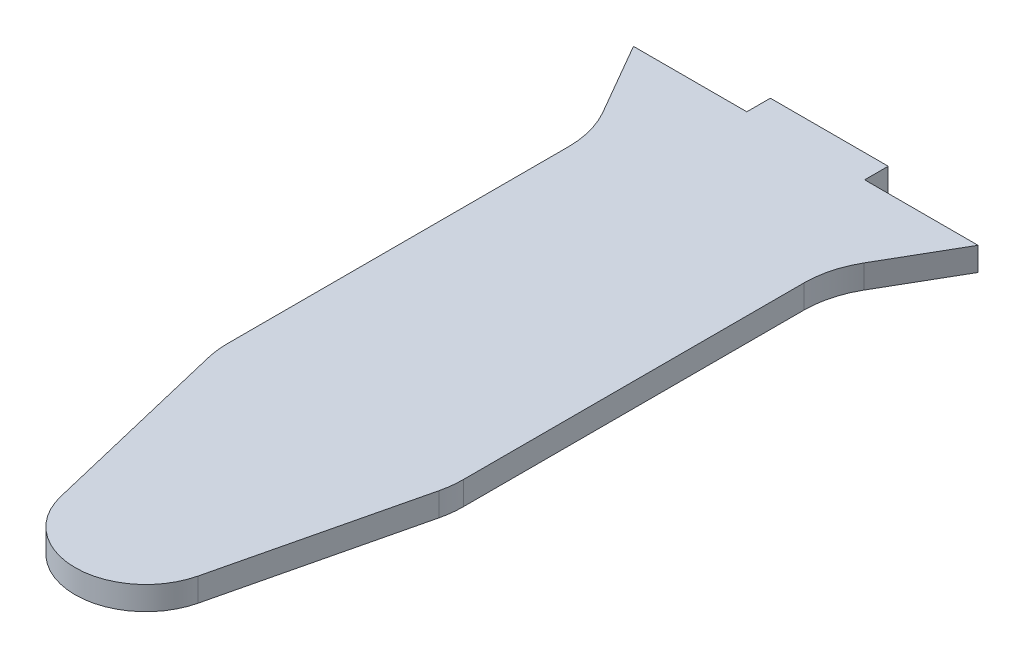
SolidWorks part; units mm, degrees
material "Pine"
ref_plane "Front Plane" through (0, 0, 0) normal (0, 0, 1) x (1, 0, 0)
ref_plane "Top Plane" through (0, 0, 0) normal (0, 1, 0) x (1, 0, 0)
ref_plane "Right Plane" through (0, 0, 0) normal (1, 0, 0) x (0, 0, -1)
sketch "Sketch2" plane through (0, 69.85, 0) normal (0, 1, 0) x (1, 0, 0)
  line L0 (-103.1875, 0) -> (103.1875, 0) construction
  line L1 (-15.875, 6.35) -> (15.875, 6.35)
  line L4 (15.875, 6.35) -> (15.875, 0)
  line L6 (31.75, -127) -> (31.75, -32.2059)
  line L10 (-15.875, 0) -> (-46.4147, 0)
  line L13 (46.4147, 0) -> (35.153, -19.5059)
  line L15 (0, 0) -> (0, -193.7253) construction
  line L16 (46.4147, 0) -> (15.875, 0)
  line L19 (-31.75, -127) -> (-31.75, -32.2059)
  line L20 (-46.4147, 0) -> (-35.153, -19.5059)
  line L23 (-15.875, 6.35) -> (-15.875, 0)
  line L25 (18.5265, -182.2353) -> (31.75, -127)
  line L27 (-18.5265, -182.2353) -> (-31.75, -127)
  arc A0 (-18.5265, -182.2353) -> (18.5265, -182.2353) centre (0, -177.8) ccw
  arc A3 (35.153, -19.5059) -> (31.75, -32.2059) centre (57.15, -32.2059) ccw
  arc A5 (-35.153, -19.5059) -> (-31.75, -32.2059) centre (-57.15, -32.2059) cw
  point P15 (31.75, -25.4)
  dimension "D1" = 38.1
  dimension "D3" = 25.4
  dimension "D5" = 127
  dimension "D2" = 177.8
  dimension "D4" = 63.5
  dimension "D6" = 25.4
  dimension "D9" = 120
extrude "Boss-Extrude1" add sketch "Sketch2" along normal blind 6.35
fillet "Fillet1" radius 25.4 2 edges at (31.75, 73.025, 127) (-31.75, 73.025, 127)
